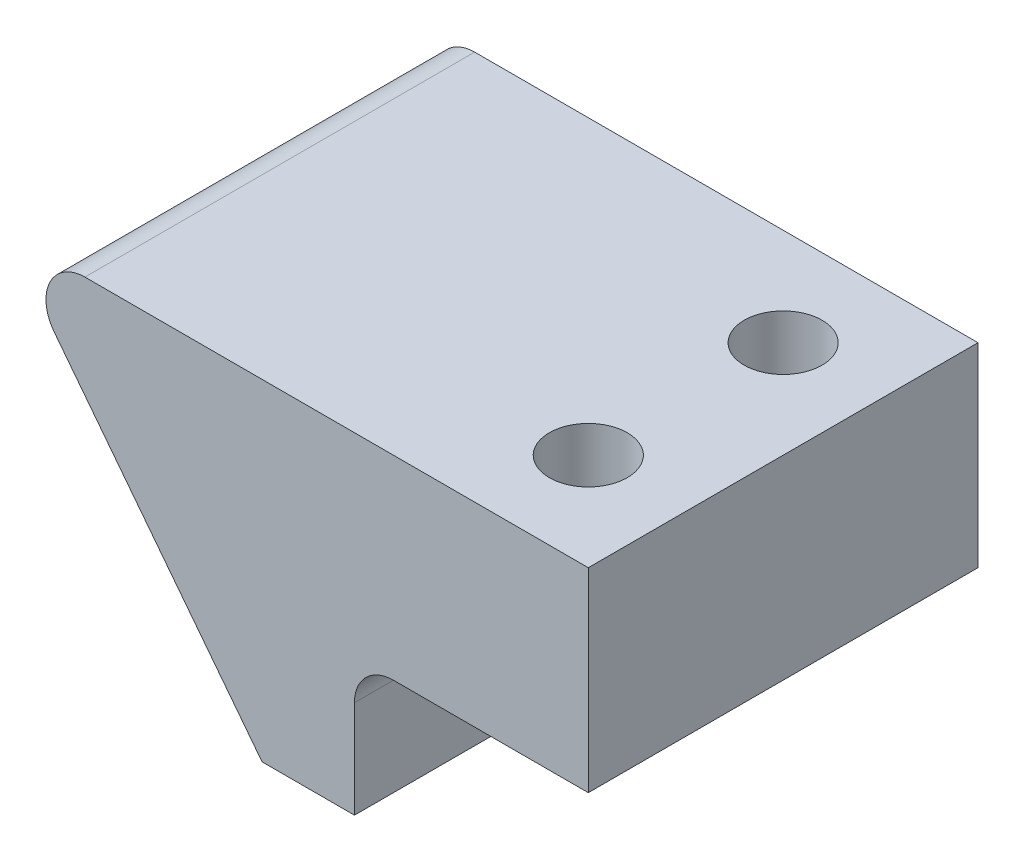
SolidWorks part; units mm, degrees
ref_plane "前视基准面" through (0, 0, 0) normal (0, 0, 1) x (1, 0, 0)
ref_plane "上视基准面" through (0, 0, 0) normal (0, 1, 0) x (1, 0, 0)
ref_plane "右视基准面" through (0, 0, 0) normal (1, 0, 0) x (0, 0, -1)
sketch "草图2" plane through (0, 0, 0) normal (0, 0, 1) x (1, 0, 0)
  line L0 (14, 0) -> (16.5882, 9.6593) construction
  line L1 (14, 0) -> (0, 0) construction
  line L2 (14, 0) -> (14, 10) construction
  line L4 (15.0441, 19) -> (30, 19)
  line L5 (30, 19) -> (30, 14)
  line L6 (30, 14) -> (24, 14)
  line L7 (24, 14) -> (24, 10.5)
  line L8 (24, 10.5) -> (21.6293, 10.5)
  line L9 (21.6293, 10.5) -> (15.0441, 19)
  circle A0 centre (16.5882, 9.6593) radius 4.5 construction
  circle A1 centre (14, 10) radius 4.5 construction
  circle A2 centre (14, 13) radius 4.5 construction
  dimension "D4" = 3.5
  dimension "D5" = 15
  dimension "D7" = 3
  dimension "D11" = 9
  dimension "D1" = 14
  dimension "D2" = 105
  dimension "D3" = 10
  dimension "D6" = 19
  dimension "D8" = 5
  dimension "D9" = 16
  dimension "D10" = 6
extrude "凸台-拉伸1" add sketch "草图2" along normal blind 5 and the other way blind 5
fillet "圆角1" radius 1 2 edges at (24, 14, 0) (15.0441, 19, 0)
hole_wizard "大小mm Clearance 暗销孔1" positions "草图3" profile "草图4" hole size "Ø2.0" standard "GB" end condition through all
sketch "草图3" plane through (0, 14, 0) normal (0, -1, 0) x (-1, 0, 0)
  line L0 (0, 0) -> (-32.6387, 0) construction
  line L2 (-30, 5) -> (-30, -5) construction
  point P0 (-27.5, 2.5)
  point P2 (-27.5, -2.5)
  point P9 (0, 0)
  dimension "D1" = 2.5
  dimension "D2" = 2.5
sketch "草图4" plane through (27.5, 14, -2.5) normal (1, 0, 0) x (0, 0, -1)
  line L0 (0, 0) -> (0, 5)
  line L1 (0, 5) -> (1, 5)
  line L2 (1, 5) -> (1, 0)
  line L5 (1, 0) -> (0, 0)
  line L11 (0, -6.35) -> (0, 107.95) construction
  dimension "通孔孔直径" = 2
  dimension "通孔孔深度" = 5
